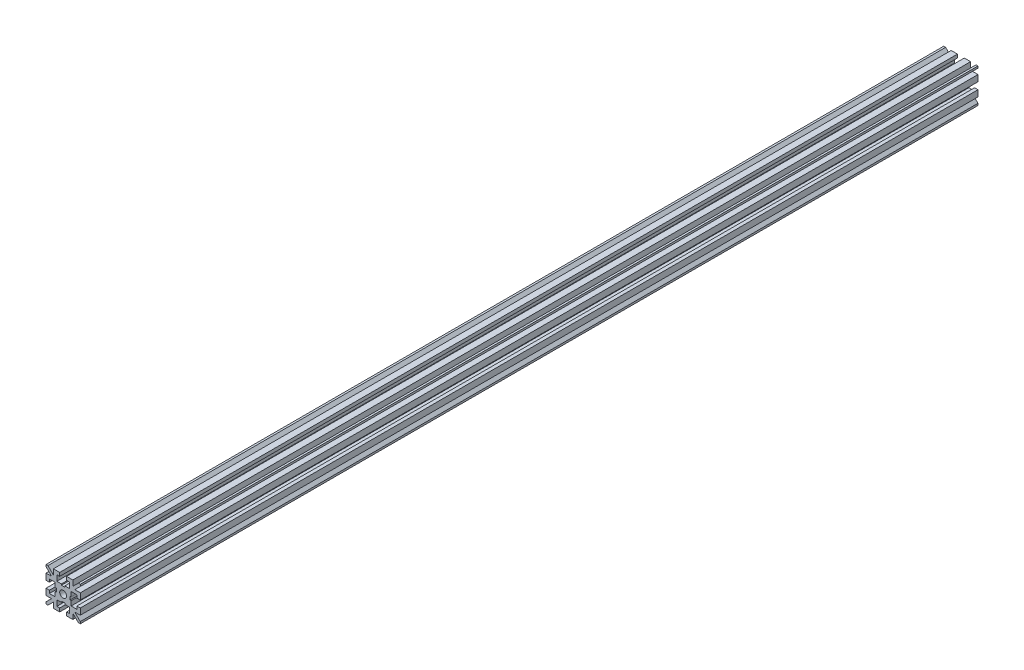
SolidWorks part; units mm, degrees
ref_plane "Front Plane" through (0, 0, 0) normal (0, 0, 1) x (1, 0, 0)
ref_plane "Top Plane" through (0, 0, 0) normal (0, 1, 0) x (1, 0, 0)
ref_plane "Right Plane" through (0, 0, 0) normal (1, 0, 0) x (0, 0, -1)
sketch "Sketch1" plane through (0, 0, 0) normal (0, 0, 1) x (1, 0, 0)
  line L1 (-9.0006, 3.7616) -> (5.9994, 3.7616)
  line L2 (-9.0006, 3.7616) -> (-9.0006, -11.2384)
  line L3 (-9.0006, -11.2384) -> (5.9994, -11.2384)
  line L4 (5.9994, 3.7616) -> (5.9994, -11.2384)
  dimension "D1" = 15
  dimension "D2" = 15
extrude "Boss-Extrude1" add sketch "Sketch1" along normal blind 393
sketch "Sketch2" plane through (0, 0, 393) normal (0, 0, 1) x (1, 0, 0)
  line L0 (-9.0006, 3.7616) -> (5.9994, -11.2384) construction
  line L1 (5.9994, 3.7616) -> (-9.0006, -11.2384) construction
  line L4 (1.9994, -4.4884) -> (1.9994, -6.4884)
  line L5 (5.9994, -3.7384) -> (1.9994, -3.7384) construction
  line L6 (5.9994, -11.2384) -> (5.9994, 3.7616) construction
  line L7 (-1.5006, 3.7616) -> (-1.5006, -3.7384) construction
  line L8 (5.9994, 3.7616) -> (-9.0006, 3.7616) construction
  line L9 (-9.0006, -3.7384) -> (-1.5006, -3.7384) construction
  line L10 (-9.0006, 3.7616) -> (-9.0006, -11.2384) construction
  line L11 (-1.5006, -11.2384) -> (-1.5006, -3.7384) construction
  line L12 (-9.0006, -11.2384) -> (5.9994, -11.2384) construction
  line L13 (1.9994, -4.4884) -> (1.4994, -4.4884)
  line L14 (1.9994, -0.9884) -> (4.4994, -0.9884)
  line L15 (1.9994, -0.9884) -> (1.9994, -2.9884)
  line L16 (1.9994, -6.4884) -> (4.4994, -6.4884)
  line L17 (4.4994, -0.9884) -> (4.4994, -6.4884)
  line L18 (-4.2506, -7.2384) -> (-4.2506, -9.7384)
  line L19 (1.9994, -2.9884) -> (1.4994, -2.9884)
  line L20 (1.4994, -4.4884) -> (1.4994, -2.9884)
  line L21 (1.4994, -3.7384) -> (-0.0006, -3.7384) construction
  line L22 (-2.2506, -7.2384) -> (-4.2506, -7.2384)
  line L23 (-2.2506, -7.2384) -> (-2.2506, -6.7384)
  line L24 (-2.2506, -6.7384) -> (-0.7506, -6.7384)
  line L25 (-0.7506, -7.2384) -> (-0.7506, -6.7384)
  line L26 (1.2494, -7.2384) -> (-0.7506, -7.2384)
  line L27 (1.2494, -7.2384) -> (1.2494, -9.7384)
  line L28 (1.2494, -9.7384) -> (-4.2506, -9.7384)
  line L29 (-5.0006, -0.9884) -> (-7.5006, -0.9884)
  line L30 (-5.0006, -2.9884) -> (-5.0006, -0.9884)
  line L31 (-5.0006, -2.9884) -> (-4.5006, -2.9884)
  line L32 (-4.5006, -2.9884) -> (-4.5006, -4.4884)
  line L33 (-5.0006, -4.4884) -> (-4.5006, -4.4884)
  line L34 (-5.0006, -6.4884) -> (-5.0006, -4.4884)
  line L35 (-5.0006, -6.4884) -> (-7.5006, -6.4884)
  line L36 (-7.5006, -6.4884) -> (-7.5006, -0.9884)
  line L37 (1.2494, -0.2384) -> (1.2494, 2.2616)
  line L38 (-0.7506, -0.2384) -> (1.2494, -0.2384)
  line L39 (-0.7506, -0.2384) -> (-0.7506, -0.7384)
  line L40 (-0.7506, -0.7384) -> (-2.2506, -0.7384)
  line L41 (-2.2506, -0.2384) -> (-2.2506, -0.7384)
  line L42 (-4.2506, -0.2384) -> (-2.2506, -0.2384)
  line L43 (-4.2506, -0.2384) -> (-4.2506, 2.2616)
  line L44 (-4.2506, 2.2616) -> (1.2494, 2.2616)
  circle A0 centre (-1.5006, -3.7384) radius 1.5
  point P60 (-1.5006, -3.7384)
  dimension "D1" = 5.5
  dimension "D2" = 2.5
  dimension "D3" = 1.5
  dimension "D4" = 2.75
  dimension "D5" = 0.5
  dimension "D6" = 1.5
  dimension "D7" = 0.75
  dimension "D8" = 4
extrude "Cut-Extrude1" cut sketch "Sketch2" against normal up to surface (393 mm away) up to face at (-1.5006, -3.7384, 0)
sketch "Sketch3" plane through (0, 0, 393) normal (0, 0, 1) x (1, 0, 0)
  line L0 (5.9994, 3.7616) -> (-9.0006, -11.2384) construction
  line L1 (-9.0006, 3.7616) -> (5.9994, -11.2384) construction
  line L2 (5.1509, 3.7616) -> (2.7494, 1.3602)
  line L3 (5.9994, 3.7616) -> (-9.0006, 3.7616) construction
  line L4 (2.7494, 1.3602) -> (2.7494, 3.7616)
  line L5 (2.7494, 3.7616) -> (5.1509, 3.7616)
  line L6 (1.2494, -0.2384) -> (1.2494, 2.2616) construction
  line L7 (5.9994, 0.5116) -> (5.9994, 2.9131)
  line L8 (3.5979, 0.5116) -> (5.9994, 0.5116)
  line L9 (5.9994, 2.9131) -> (3.5979, 0.5116)
  line L10 (1.2494, 2.2616) -> (-4.2506, 2.2616) construction
  line L11 (-3.0006, 3.7616) -> (-0.0006, 3.7616)
  line L12 (-3.0006, 3.7616) -> (-3.0006, 2.2616)
  line L13 (-3.0006, 2.2616) -> (-0.0006, 2.2616)
  line L14 (-0.0006, 3.7616) -> (-0.0006, 2.2616)
  line L15 (-2.2506, -0.7384) -> (-0.7506, -0.7384) construction
  line L16 (2.7494, -8.8369) -> (2.7494, -11.2384)
  line L17 (2.7494, -11.2384) -> (5.1509, -11.2384)
  line L18 (5.1509, -11.2384) -> (2.7494, -8.8369)
  line L19 (5.9994, -10.3898) -> (3.5979, -7.9884)
  line L20 (3.5979, -7.9884) -> (5.9994, -7.9884)
  line L21 (5.9994, -7.9884) -> (5.9994, -10.3898)
  line L22 (5.9994, -5.2384) -> (4.4994, -5.2384)
  line L23 (5.9994, -2.2384) -> (5.9994, -5.2384)
  line L24 (5.9994, -2.2384) -> (4.4994, -2.2384)
  line L25 (4.4994, -2.2384) -> (4.4994, -5.2384)
  line L26 (-6.5991, -7.9884) -> (-9.0006, -7.9884)
  line L27 (-9.0006, -7.9884) -> (-9.0006, -10.3898)
  line L28 (-9.0006, -10.3898) -> (-6.5991, -7.9884)
  line L29 (-8.1521, -11.2384) -> (-5.7506, -8.8369)
  line L30 (-5.7506, -8.8369) -> (-5.7506, -11.2384)
  line L31 (-5.7506, -11.2384) -> (-8.1521, -11.2384)
  line L32 (-3.0006, -11.2384) -> (-3.0006, -9.7384)
  line L33 (-0.0006, -11.2384) -> (-3.0006, -11.2384)
  line L34 (-0.0006, -11.2384) -> (-0.0006, -9.7384)
  line L35 (-0.0006, -9.7384) -> (-3.0006, -9.7384)
  line L36 (-5.7506, 1.3602) -> (-5.7506, 3.7616)
  line L37 (-5.7506, 3.7616) -> (-8.1521, 3.7616)
  line L38 (-8.1521, 3.7616) -> (-5.7506, 1.3602)
  line L39 (-9.0006, 2.9131) -> (-6.5991, 0.5116)
  line L40 (-6.5991, 0.5116) -> (-9.0006, 0.5116)
  line L41 (-9.0006, 0.5116) -> (-9.0006, 2.9131)
  line L42 (-9.0006, -2.2384) -> (-7.5006, -2.2384)
  line L43 (-9.0006, -5.2384) -> (-9.0006, -2.2384)
  line L44 (-9.0006, -5.2384) -> (-7.5006, -5.2384)
  line L45 (-7.5006, -5.2384) -> (-7.5006, -2.2384)
  point P24 (-1.5006, -0.7384)
  point P27 (-1.5006, -3.7384)
  point P61 (-1.5006, -3.7384)
  dimension "D1" = 0.6
  dimension "D2" = 1.5
  dimension "D3" = 3
  dimension "D4" = 1.5
  dimension "D5" = 4
extrude "Cut-Extrude2" cut sketch "Sketch3" against normal up to surface (393 mm away) up to face at (-1.5006, 0.2616, 0)
